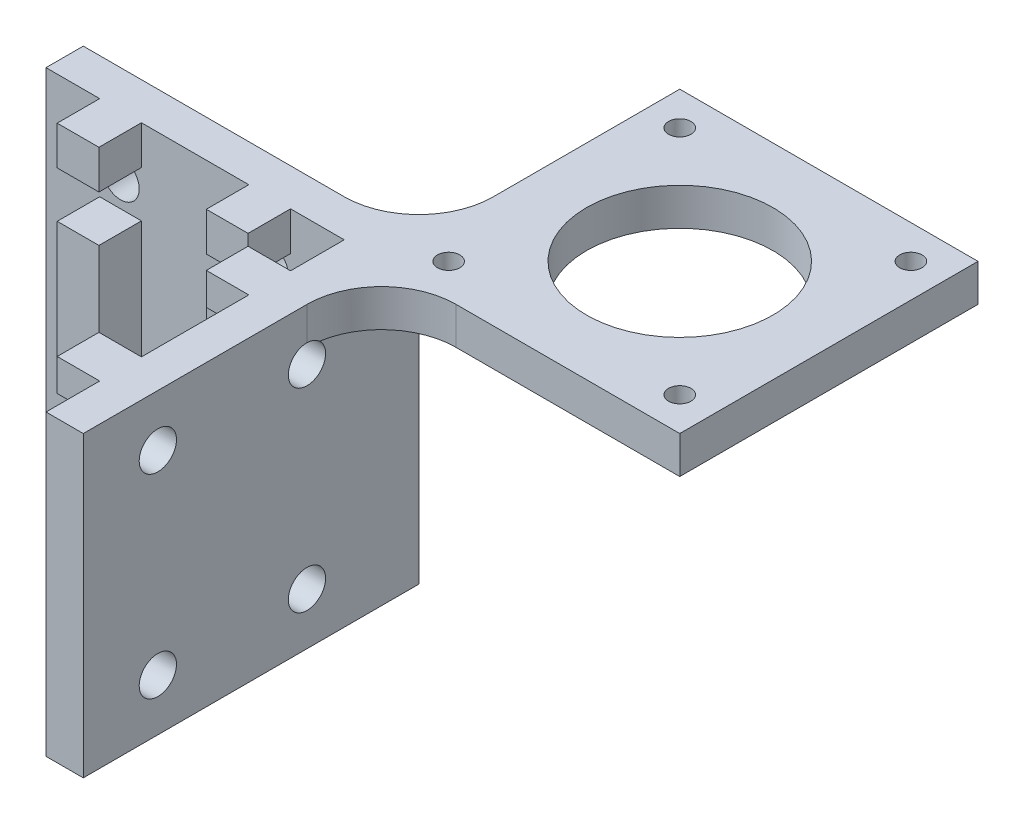
SolidWorks part; units mm, degrees
ref_plane "Alzado" through (0, 0, 0) normal (0, 0, 1) x (1, 0, 0)
ref_plane "Planta" through (0, 0, 0) normal (0, 1, 0) x (1, 0, 0)
ref_plane "Vista lateral" through (0, 0, 0) normal (1, 0, 0) x (0, 0, -1)
sketch "Croquis1" plane through (0, 0, 0) normal (0, 0, 1) x (1, 0, 0)
  line L1 (22.5, 20) -> (-22.5, 20)
  line L2 (22.5, 20) -> (22.5, -20)
  line L3 (22.5, -20) -> (-22.5, -20)
  line L4 (-22.5, 20) -> (-22.5, -20)
  line L5 (22.5, 20) -> (-22.5, -20) construction
  line L6 (22.5, -20) -> (-22.5, 20) construction
  point P0 (0, 0)
  dimension "D1" = 45
  dimension "D2" = 40
extrude "Saliente-Extruir1" add sketch "Croquis1" along normal blind 5
sketch "Croquis2" plane through (0, 0, 5) normal (0, 0, 1) x (1, 0, 0)
  line L0 (-22.5, -20) -> (22.5, -20) construction
  line L1 (22.5, 20) -> (17.5, 20)
  line L2 (22.5, 20) -> (22.5, -20)
  line L3 (22.5, -20) -> (17.5, -20)
  line L4 (17.5, 20) -> (17.5, -20)
  dimension "D1" = 5
extrude "Saliente-Extruir2" add sketch "Croquis2" along normal blind 40
sketch "Croquis13" plane through (22.5, 0, 0) normal (1, 0, 0) x (0, 0, -1)
  line L12 (-45, -20) -> (-45, 20) construction
  line L14 (-45, 20) -> (0, 20) construction
  line L15 (35, 20) -> (-5, 20)
  line L16 (35, 20) -> (35, 15)
  line L17 (35, 15) -> (-5, 15)
  line L18 (-5, 20) -> (-5, 15)
  line L19 (35, 20) -> (-5, 15) construction
  line L20 (35, 15) -> (-5, 20) construction
  point P0 (15, 17.5)
  dimension "D1" = 40
  dimension "D2" = 40
  dimension "D3" = 5
extrude "Saliente-Extruir7" add sketch "Croquis13" along normal blind 40
sketch "Croquis15" plane through (0, 20, 0) normal (0, 1, 0) x (1, 0, 0)
  line L0 (62.5, 35) -> (62.5, -5) construction
  line L1 (62.5, -5) -> (22.5, -5) construction
  circle A0 centre (42.5, 15) radius 12.5
  dimension "D3" = 25
  dimension "D1" = 20
  dimension "D2" = 20
extrude "Cortar-Extruir3" cut sketch "Croquis15" against normal up to next
sketch "Croquis16" plane through (0, 20, 0) normal (0, 1, 0) x (1, 0, 0)
  line L1 (27, 30.5) -> (58, 30.5) construction
  line L2 (27, 30.5) -> (27, -0.5) construction
  line L3 (27, -0.5) -> (58, -0.5) construction
  line L4 (58, 30.5) -> (58, -0.5) construction
  line L5 (27, 30.5) -> (58, -0.5) construction
  line L6 (27, -0.5) -> (58, 30.5) construction
  circle A0 centre (42.5, 15) radius 12.5 construction
  point P0 (42.5, 15)
  dimension "D1" = 31
  dimension "D2" = 31
sketch "Croquis18" plane through (0, 20, 0) normal (0, 1, 0) x (1, 0, 0)
  circle A0 centre (27, 30.5) radius 1.5
  circle A1 centre (58, 30.5) radius 1.5
  circle A2 centre (58, -0.5) radius 1.5
  circle A3 centre (27, -0.5) radius 1.5
  dimension "D1" = 3
  dimension "D2" = 3
  dimension "D3" = 3
  dimension "D4" = 3
extrude "Cortar-Extruir4" cut sketch "Croquis18" against normal up to next
sketch "Croquis24" plane through (0, -20, 0) normal (0, -1, 0) x (-1, 0, 0)
  line L0 (22.5, -5) -> (-17.5, -5) construction
  line L1 (9.7, -5) -> (15.3, -5)
  line L2 (9.7, -5) -> (9.7, -10.7)
  line L3 (9.7, -10.7) -> (15.3, -10.7)
  line L4 (15.3, -5) -> (15.3, -10.7)
  line L5 (9.7, -5) -> (15.3, -10.7) construction
  line L6 (9.7, -10.7) -> (15.3, -5) construction
  line L7 (-10.3, -5) -> (-4.7, -5)
  line L8 (-10.3, -5) -> (-10.3, -10.7)
  line L9 (-10.3, -10.7) -> (-4.7, -10.7)
  line L10 (-4.7, -5) -> (-4.7, -10.7)
  line L11 (-10.3, -5) -> (-4.7, -10.7) construction
  line L12 (-10.3, -10.7) -> (-4.7, -5) construction
  line L13 (-17.5, -32.2) -> (-11.8, -32.2)
  line L14 (-17.5, -32.2) -> (-17.5, -37.8)
  line L15 (-17.5, -37.8) -> (-11.8, -37.8)
  line L16 (-11.8, -32.2) -> (-11.8, -37.8)
  line L17 (-17.5, -32.2) -> (-11.8, -37.8) construction
  line L18 (-17.5, -37.8) -> (-11.8, -32.2) construction
  line L19 (-17.5, -17.8) -> (-11.8, -17.8)
  line L20 (-17.5, -17.8) -> (-17.5, -12.2)
  line L21 (-17.5, -12.2) -> (-11.8, -12.2)
  line L22 (-11.8, -17.8) -> (-11.8, -12.2)
  line L23 (-17.5, -17.8) -> (-11.8, -12.2) construction
  line L24 (-17.5, -12.2) -> (-11.8, -17.8) construction
  line L25 (22.5, -5) -> (22.5, 0) construction
  line L26 (-17.5, -45) -> (-17.5, -5) construction
  line L27 (-17.5, -45) -> (-22.5, -45) construction
  point P0 (12.5, -7.85)
  point P5 (-7.5, -7.85)
  point P10 (-14.65, -35)
  point P15 (-14.65, -15)
  dimension "D1" = 10
  dimension "D2" = 20
  dimension "D3" = 10
  dimension "D4" = 20
  dimension "D5" = 5.6
  dimension "D6" = 5.7
  dimension "D7" = 5.6
  dimension "D8" = 5.6
  dimension "D9" = 5.7
  dimension "D10" = 5.6
extrude "Saliente-Extruir8" add sketch "Croquis24" against normal up to surface (40 mm away) up to face at (25.5, 20, 0.5)
sketch "Croquis20" plane through (11.8, 0, 0) normal (-1, 0, 0) x (0, 0, 1)
  line L0 (45, 20) -> (37.8, 20) construction
  line L1 (5, -15.7) -> (45, -15.7)
  line L2 (5, -15.7) -> (5, -9.5)
  line L3 (5, -9.5) -> (45, -9.5)
  line L4 (45, -15.7) -> (45, -9.5)
  line L5 (5, 20) -> (5, -20) construction
  line L6 (45, 20) -> (45, -20) construction
  line L8 (32.2, -20) -> (17.8, -20) construction
  line L9 (5, 9.5) -> (45, 9.5)
  line L10 (5, 9.5) -> (5, 15.7)
  line L11 (5, 15.7) -> (45, 15.7)
  line L12 (45, 9.5) -> (45, 15.7)
  line L14 (5, 20) -> (5, -20) construction
  dimension "D1" = 6.2
  dimension "D2" = 4.3
  dimension "D3" = 4.3
  dimension "D4" = 6.2
extrude "Cortar-Extruir5" cut sketch "Croquis20" against normal up to surface (5.7 mm away) contours L1 L4 L3 | L3 L1 | L3 L2 L1 | L9 L12 L11 | L11 L9 | L11 L10 L9 region at (11.8, -12.6, 25) region at (11.8, 12.6, 25) up to face at (17.5, 0, 25)
sketch "Croquis21" plane through (0, 0, 10.7) normal (0, 0, 1) x (1, 0, 0)
  line L0 (-22.5, -20) -> (-15.3, -20) construction
  line L1 (-22.5, -15.7) -> (17.5, -15.7)
  line L2 (-22.5, -15.7) -> (-22.5, -9.5)
  line L3 (-22.5, -9.5) -> (17.5, -9.5)
  line L4 (17.5, -15.7) -> (17.5, -9.5)
  line L5 (-22.5, 20) -> (-22.5, -20) construction
  line L6 (17.5, 20) -> (17.5, -20) construction
  line L7 (-15.3, 20) -> (-22.5, 20) construction
  line L8 (-22.5, 8.6) -> (17.5, 8.6)
  line L9 (-22.5, 8.6) -> (-22.5, 14.8)
  line L10 (-22.5, 14.8) -> (17.5, 14.8)
  line L11 (17.5, 8.6) -> (17.5, 14.8)
  dimension "D1" = 4.3
  dimension "D2" = 6.2
  dimension "D3" = 5.2
  dimension "D4" = 6.2
extrude "Cortar-Extruir6" cut sketch "Croquis21" against normal up to surface (5.7 mm away) contours L3 L2 L1 | L3 L1 | L1 L4 L3 | L10 L9 L8 | L10 L8 | L8 L11 L10 region at (-2.5, -12.6, 10.7) region at (-2.5, 11.7, 10.7) up to face at (-2.5, 0, 5)
sketch "Croquis22" plane through (17.5, 0, 0) normal (-1, 0, 0) x (0, 0, 1)
  line L0 (45, 20) -> (45, -20) construction
  line L3 (45, 20) -> (37.8, 20) construction
  line L5 (45, -20) -> (37.8, -20) construction
  circle A0 centre (15, 13.05) radius 2.5
  circle A1 centre (35, 13.05) radius 2.5
  circle A2 centre (15, -13.05) radius 2.5
  circle A3 centre (35, -13.05) radius 2.5
  dimension "D1" = 5
  dimension "D2" = 10
  dimension "D3" = 6.95
  dimension "D4" = 20
  dimension "D5" = 6.95
extrude "Cortar-Extruir7" cut sketch "Croquis22" against normal up to next
sketch "Croquis23" plane through (0, 0, 5) normal (0, 0, 1) x (1, 0, 0)
  line L0 (-22.5, 20) -> (-22.5, -20) construction
  line L1 (-15.3, 20) -> (-9.7, 20) construction
  line L2 (-9.7, -20) -> (-15.3, -20) construction
  circle A0 centre (-12.5, 12.15) radius 2.5
  circle A1 centre (7.5, 12.15) radius 2.5
  circle A2 centre (-12.5, -13.05) radius 2.5
  circle A3 centre (7.5, -13.05) radius 2.5
  dimension "D1" = 5
  dimension "D2" = 10
  dimension "D3" = 7.85
  dimension "D4" = 20
  dimension "D5" = 6.95
extrude "Cortar-Extruir8" cut sketch "Croquis23" against normal up to next
fillet "Redondeo1" radius 10 1 edges at (22.5, 17.5, 5)
fillet "Redondeo2" radius 10 1 edges at (22.5, 17.5, 0)
